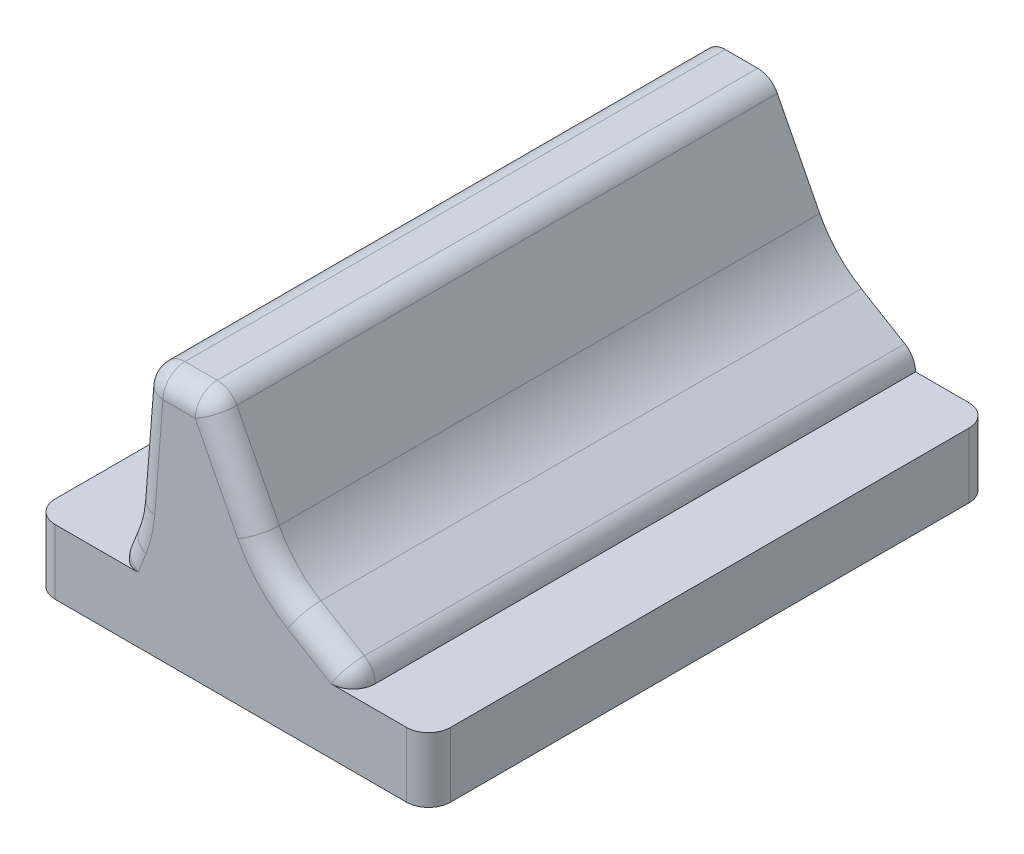
SolidWorks part; units mm, degrees
ref_plane "Plan de face" through (0, 0, 0) normal (0, 0, 1) x (1, 0, 0)
ref_plane "Plan de dessus" through (0, 0, 0) normal (0, 1, 0) x (1, 0, 0)
ref_plane "Plan de droite" through (0, 0, 0) normal (1, 0, 0) x (0, 0, -1)
sketch "Esquisse1" plane through (0, 0, 0) normal (0, 0, 1) x (1, 0, 0)
  line L0 (-5.1854, 1.525) -> (-5.1854, 1.576) construction
  line L1 (-5.1153, 1.9437) -> (-4.7761, 2.8016) construction
  line L2 (-4.4412, 4.2487) -> (-4.0724, 8.9461) construction
  line L3 (-3.0754, 9.8678) -> (-1.6111, 9.8678) construction
  line L4 (3.0886, 3.5606) -> (5.0604, 2.3837) construction
  line L5 (5.5479, 1.525) -> (7.9662, 1.525) construction
  line L6 (8.9662, 1.525) -> (7.9662, 1.525) construction
  line L7 (8.9662, 1.525) -> (8.9662, -1.4124) construction
  line L8 (7.9662, -1.4124) -> (8.9662, -1.4124) construction
  line L9 (7.9662, -1.4124) -> (4, -1.4124) construction
  line L10 (-4, -1.4124) -> (-7.9662, -1.4124) construction
  line L11 (-8.9662, -1.4124) -> (-7.9662, -1.4124) construction
  line L12 (-8.9662, -1.4124) -> (-8.9662, 1.525) construction
  line L13 (-7.9662, 1.525) -> (-8.9662, 1.525) construction
  line L14 (-7.9662, 1.525) -> (-5.1854, 1.525) construction
  line L15 (-5.1854, 1.525) -> (-5.1854, 1.576)
  line L16 (-5.1153, 1.9437) -> (-4.7761, 2.8016)
  line L17 (-4.4412, 4.2487) -> (-4.0724, 8.9461)
  line L18 (-3.0754, 9.8678) -> (-1.6111, 9.8678)
  line L19 (3.0886, 3.5606) -> (5.0604, 2.3837)
  line L20 (5.5479, 1.525) -> (7.9662, 1.525)
  line L21 (8.9662, 1.525) -> (7.9662, 1.525)
  line L22 (8.9662, 1.525) -> (8.9662, -1.4124)
  line L23 (7.9662, -1.4124) -> (8.9662, -1.4124)
  line L24 (7.9662, -1.4124) -> (4, -1.4124)
  line L25 (-4, -1.4124) -> (-7.9662, -1.4124)
  line L26 (-8.9662, -1.4124) -> (-7.9662, -1.4124)
  line L27 (-8.9662, -1.4124) -> (-8.9662, 1.525)
  line L28 (-7.9662, 1.525) -> (-8.9662, 1.525)
  line L29 (-7.9662, 1.525) -> (-5.1854, 1.525)
  line L30 (4, -1.4124) -> (4, 0) construction
  line L31 (1, 0) -> (8, 0) construction
  line L32 (8, 1) -> (8, 0) construction
  line L33 (1, 1) -> (8, 1) construction
  line L34 (4, 1.202) -> (4, 1) construction
  line L35 (-2.798, 9) -> (-1.798, 9) construction
  line L36 (-4, 1) -> (-4, 1.5) construction
  line L37 (-8, 1) -> (-1, 1) construction
  line L38 (-8, 1) -> (-8, 0) construction
  line L39 (-8, 0) -> (-1, 0) construction
  line L40 (-4, 0) -> (-4, -1.4124) construction
  line L41 (4, -1.4124) -> (4, 0)
  line L42 (4, 0) -> (8, 0)
  line L43 (8, 1) -> (8, 0)
  line L44 (4, 1) -> (8, 1)
  line L45 (4, 1.202) -> (4, 1)
  line L46 (-2.798, 9) -> (-1.798, 9)
  line L47 (-4, 1) -> (-4, 1.5)
  line L48 (-8, 1) -> (-4, 1)
  line L49 (-8, 1) -> (-8, 0)
  line L50 (-8, 0) -> (-4, 0)
  line L51 (-4, 0) -> (-4, -1.4124)
  line L52 (-0.7212, 9.324) -> (1.2015, 5.5732)
  arc A0 (-5.1153, 1.9437) -> (-5.1854, 1.576) centre (-4.1854, 1.576) ccw construction
  arc A1 (-4.7761, 2.8016) -> (-4.4412, 4.2487) centre (-9.4259, 4.6401) ccw construction
  arc A2 (-3.0754, 9.8678) -> (-4.0724, 8.9461) centre (-3.0754, 8.8678) ccw construction
  arc A3 (-0.7212, 9.324) -> (-1.6111, 9.8678) centre (-1.6111, 8.8678) ccw construction
  arc A4 (1.2015, 5.5732) -> (3.0886, 3.5606) centre (5.651, 7.854) ccw construction
  arc A5 (5.5479, 1.525) -> (5.0604, 2.3837) centre (4.5479, 1.525) ccw construction
  arc A6 (-5.1153, 1.9437) -> (-5.1854, 1.576) centre (-4.1854, 1.576) ccw
  arc A7 (-4.7761, 2.8016) -> (-4.4412, 4.2487) centre (-9.4259, 4.6401) ccw
  arc A8 (-3.0754, 9.8678) -> (-4.0724, 8.9461) centre (-3.0754, 8.8678) ccw
  arc A9 (-0.7212, 9.324) -> (-1.6111, 9.8678) centre (-1.6111, 8.8678) ccw
  arc A10 (1.2015, 5.5732) -> (3.0886, 3.5606) centre (5.651, 7.854) ccw
  arc A11 (5.5479, 1.525) -> (5.0604, 2.3837) centre (4.5479, 1.525) ccw
  arc A12 (4, 1.202) -> (3.4545, 2.0928) centre (3, 1.202) ccw construction
  arc A13 (-1.798, 9) -> (3.4545, 2.0928) centre (8, 11) ccw construction
  arc A14 (-2.798, 9) -> (-3.035, 3.8221) centre (6.7317, 5.9694) ccw construction
  arc A15 (-3.6, 2.3) -> (-3.035, 3.8221) centre (-4.5, 3.5) ccw construction
  arc A16 (-3.6, 2.3) -> (-4, 1.5) centre (-3, 1.5) ccw construction
  arc A17 (4, 1.202) -> (3.4545, 2.0928) centre (3, 1.202) ccw
  arc A18 (-1.798, 9) -> (3.4545, 2.0928) centre (8, 11) ccw
  arc A19 (-2.798, 9) -> (-3.035, 3.8221) centre (6.7317, 5.9694) ccw
  arc A20 (-3.6, 2.3) -> (-3.035, 3.8221) centre (-4.5, 3.5) ccw
  arc A21 (-3.6, 2.3) -> (-4, 1.5) centre (-3, 1.5) ccw
extrude "Extrusion1" add sketch "Esquisse1" against normal blind 24
sketch "Esquisse2" plane through (0, 0, 0) normal (0, 0, 1) x (1, 0, 0)
  line L0 (-4, -1.4124) -> (4, -1.4124)
  line L23 (-5.1854, 1.576) -> (-5.1854, 1.525)
  line L24 (-5.1854, 1.525) -> (-8.9662, 1.525)
  line L25 (-8.9662, 1.525) -> (-8.9662, -1.4124)
  line L26 (-8.9662, -1.4124) -> (-4, -1.4124)
  line L27 (-4, -1.4124) -> (-4, 0)
  line L28 (-4, 0) -> (-8, 0)
  line L29 (-8, 0) -> (-8, 1)
  line L30 (-8, 1) -> (-4, 1)
  line L31 (-4, 1) -> (-4, 1.5)
  line L32 (-2.798, 9) -> (-1.798, 9)
  line L33 (4, 1.202) -> (4, 1)
  line L34 (4, 1) -> (8, 1)
  line L35 (8, 1) -> (8, 0)
  line L36 (8, 0) -> (4, 0)
  line L37 (4, 0) -> (4, -1.4124)
  line L38 (4, -1.4124) -> (8.9662, -1.4124)
  line L39 (8.9662, -1.4124) -> (8.9662, 1.525)
  line L40 (8.9662, 1.525) -> (5.5479, 1.525)
  line L41 (5.0604, 2.3837) -> (3.0886, 3.5606)
  line L42 (1.2015, 5.5732) -> (-0.7212, 9.324)
  line L43 (-1.6111, 9.8678) -> (-3.0754, 9.8678)
  line L44 (-4.0724, 8.9461) -> (-4.4412, 4.2487)
  line L45 (-4.7761, 2.8016) -> (-5.1153, 1.9437)
  line L46 (-5.1854, 1.576) -> (-5.1854, 1.525)
  line L47 (-5.1854, 1.525) -> (-8.9662, 1.525)
  line L48 (-8.9662, 1.525) -> (-8.9662, -1.4124)
  line L49 (-8.9662, -1.4124) -> (-4, -1.4124)
  line L61 (4, -1.4124) -> (8.9662, -1.4124)
  line L62 (8.9662, -1.4124) -> (8.9662, 1.525)
  line L63 (8.9662, 1.525) -> (5.5479, 1.525)
  line L64 (5.0604, 2.3837) -> (3.0886, 3.5606)
  line L65 (1.2015, 5.5732) -> (-0.7212, 9.324)
  line L66 (-1.6111, 9.8678) -> (-3.0754, 9.8678)
  line L67 (-4.0724, 8.9461) -> (-4.4412, 4.2487)
  line L68 (-4.7761, 2.8016) -> (-5.1153, 1.9437)
  arc A11 (-3.6, 2.3) -> (-4, 1.5) centre (-3, 1.5) ccw
  arc A12 (-3.6, 2.3) -> (-3.035, 3.8221) centre (-4.5, 3.5) ccw
  arc A13 (-2.798, 9) -> (-3.035, 3.8221) centre (6.7317, 5.9694) ccw
  arc A14 (-1.798, 9) -> (3.4545, 2.0928) centre (8, 11) ccw
  arc A15 (4, 1.202) -> (3.4545, 2.0928) centre (3, 1.202) ccw
  arc A16 (5.5479, 1.525) -> (5.0604, 2.3837) centre (4.5479, 1.525) ccw
  arc A17 (1.2015, 5.5732) -> (3.0886, 3.5606) centre (5.651, 7.854) ccw
  arc A18 (-0.7212, 9.324) -> (-1.6111, 9.8678) centre (-1.6111, 8.8678) ccw
  arc A19 (-3.0754, 9.8678) -> (-4.0724, 8.9461) centre (-3.0754, 8.8678) ccw
  arc A20 (-4.7761, 2.8016) -> (-4.4412, 4.2487) centre (-9.4259, 4.6401) ccw
  arc A21 (-5.1153, 1.9437) -> (-5.1854, 1.576) centre (-4.1854, 1.576) ccw
  arc A27 (5.5479, 1.525) -> (5.0604, 2.3837) centre (4.5479, 1.525) ccw
  arc A28 (1.2015, 5.5732) -> (3.0886, 3.5606) centre (5.651, 7.854) ccw
  arc A29 (-0.7212, 9.324) -> (-1.6111, 9.8678) centre (-1.6111, 8.8678) ccw
  arc A30 (-3.0754, 9.8678) -> (-4.0724, 8.9461) centre (-3.0754, 8.8678) ccw
  arc A31 (-4.7761, 2.8016) -> (-4.4412, 4.2487) centre (-9.4259, 4.6401) ccw
  arc A32 (-5.1153, 1.9437) -> (-5.1854, 1.576) centre (-4.1854, 1.576) ccw
  dimension "D1" = 0
extrude "Extrusion2" add sketch "Esquisse2" along normal blind 1.5
fillet "Congé1" radius 1 5 edges at (-8.9662, 0.0563, -24) (8.9662, 0.0563, -24) (8.9662, 0.0563, 1.5) (-8.9662, 0.0563, 1.5) (-2.3433, 9.8678, 1.5)
